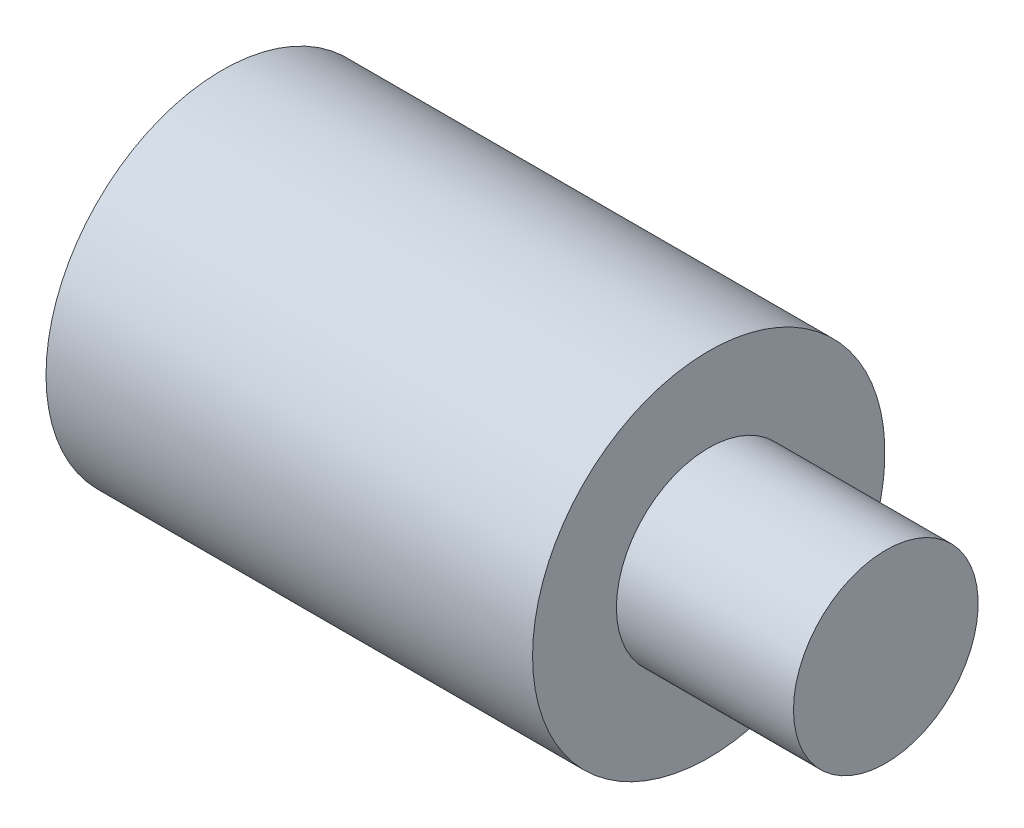
SolidWorks part; units mm, degrees
ref_plane "Front Plane" through (0, 0, 0) normal (0, 0, 1) x (1, 0, 0)
ref_plane "Top Plane" through (0, 0, 0) normal (0, 1, 0) x (1, 0, 0)
ref_plane "Right Plane" through (0, 0, 0) normal (1, 0, 0) x (0, 0, -1)
sketch "Conn_T6_ORB4 Sketch" plane through (0, 0, 0) normal (0, 0, 1) x (1, 0, 0)
  line L0 (-1000, 0) -> (1000, 0) construction
  line L1 (9.5, 0) -> (9.5, 4.953)
  line L2 (9.5, 4.953) -> (0, 4.953)
  line L3 (0, 4.953) -> (0, 9.45)
  line L4 (0, 9.45) -> (-26.1, 9.45)
  line L5 (-26.1, 9.45) -> (-26.1, 0)
  line L6 (-26.1, 0) -> (9.5, 0)
revolve "Conn_T6_ORB4" add sketch "Conn_T6_ORB4 Sketch" angle 360 about L0
ref_axis "Engine Axis" through (11.28, 0, 0) along (-1, 0, 0)
sketch "Socket Sketch" plane through (0, 0, 0) normal (0, 0, 1) x (1, 0, 0)
  line L0 (-1000, 0) -> (1000, 0) construction
  line L1 (-27.1, 0) -> (-27.1, 4.7625)
  line L2 (-27.1, 4.7625) -> (-9.3, 4.7625)
  line L3 (-9.3, 4.7625) -> (-9.3, 0)
  line L4 (-9.3, 0) -> (-27.1, 0)
revolve "Socket" cut sketch "Socket Sketch" angle 360 about L0
